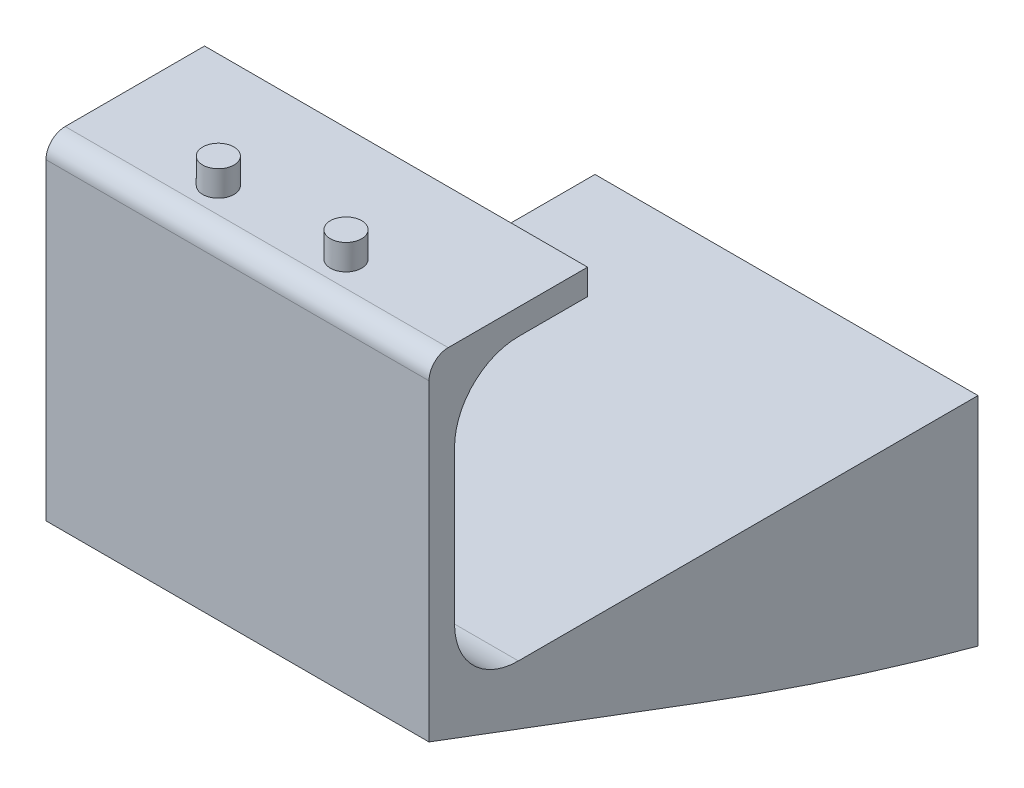
SolidWorks part; units mm, degrees
ref_plane "Front Plane" through (0, 0, 0) normal (0, 0, 1) x (1, 0, 0)
ref_plane "Top Plane" through (0, 0, 0) normal (0, 1, 0) x (1, 0, 0)
ref_plane "Right Plane" through (0, 0, 0) normal (1, 0, 0) x (0, 0, -1)
ref_plane "Plane1" through (18, 0, 0) normal (-1, 0, 0) x (0, -1, 0)
sketch "Sketch1" plane through (18, 0, 0) normal (-1, 0, 0) x (0, -1, 0)
  line L0 (-0.8382, 3) -> (-0.8382, 0)
  line L1 (-0.8382, 0) -> (0, 0)
  arc A0 (0, 0) -> (-0.8382, 3) centre (-236.8592, -64.5597) ccw
extrude "Boss-Extrude1" add sketch "Sketch1" against normal blind 24
sketch "Sketch2" plane through (0, 0.8382, 0) normal (0, 1, 0) x (-1, 0, 0)
  line L0 (-42, 21.6411) -> (-18, 21.6411)
  line L1 (-18, 21.6411) -> (-18, 0)
  line L2 (-18, 0) -> (-42, 0)
  line L3 (-42, 0) -> (-42, 21.6411)
extrude "Boss-Extrude2" add sketch "Sketch2" along normal blind 14.1618
sketch "Sketch3" plane through (42, 0, 0) normal (1, 0, 0) x (0, 0, -1)
  line L0 (0, 15) -> (0, 0)
  line L1 (-21.6411, 6.9904) -> (-43, 15)
  line L2 (-43, 15) -> (0, 15)
  arc A0 (0, 0) -> (-21.6411, 6.9904) centre (64.5597, 236.8592) cw
extrude "Boss-Extrude3" add sketch "Sketch3" along normal blind 3
sketch "Sketch4" plane through (0, 0, 21.6411) normal (0, 0, 1) x (1, 0, 0)
  line L0 (42, 15) -> (42, 6.9904)
  line L1 (42, 6.9904) -> (42, 0.8382)
  line L2 (42, 0.8382) -> (18, 0.8382)
  line L3 (18, 0.8382) -> (18, 6.9904)
  line L4 (18, 6.9904) -> (18, 15)
  line L5 (18, 15) -> (42, 15)
extrude "Boss-Extrude4" add sketch "Sketch4" along normal blind 21.3589
sketch "Sketch5" plane through (0, 15, 0) normal (0, 1, 0) x (-1, 0, 0)
  line L0 (-18, 0) -> (-45, 0)
  line L1 (-45, 0) -> (-45, 43)
  line L2 (-45, 43) -> (-18, 43)
  line L3 (-18, 43) -> (-18, 0)
extrude "Boss-Extrude5" add sketch "Sketch5" along normal blind 24
sketch "Sketch6" plane through (0, 0.8382, 0) normal (0, -1, 0) x (1, 0, 0)
  line L0 (18, 3) -> (42, 3)
  line L1 (42, 3) -> (42, 21.6411)
  line L2 (42, 21.6411) -> (42, 43)
  line L3 (42, 43) -> (18, 43)
  line L4 (18, 43) -> (18, 3)
extrude "Cut-Extrude1" cut sketch "Sketch6" against normal blind 6.1522
sketch "Sketch7" plane through (0, 6.9904, 0) normal (0, -1, 0) x (1, 0, 0)
  line L0 (18, 3) -> (42, 3)
  line L1 (42, 3) -> (42, 43)
  line L2 (42, 43) -> (18, 43)
  line L3 (18, 43) -> (18, 3)
extrude "Cut-Extrude2" cut sketch "Sketch7" against normal blind 8.0096
sketch "Sketch8" plane through (18, 0, 0) normal (-1, 0, 0) x (0, 0, 1)
  line L0 (0, 39) -> (43, 39)
  line L1 (43, 39) -> (43, 15)
  line L2 (43, 15) -> (21.6411, 6.9904)
  line L3 (0, 0) -> (0, 39)
  arc A0 (21.6411, 6.9904) -> (0, 0) centre (-64.5597, 236.8592) cw
extrude "Boss-Extrude6" add sketch "Sketch8" along normal blind 3
sketch "Sketch9" plane through (15, 0, 0) normal (-1, 0, 0) x (0, 0, 1)
  line L0 (0, 17) -> (41, 17)
  line L1 (41, 17) -> (41, 39)
  line L2 (41, 39) -> (0, 39)
  line L3 (0, 39) -> (0, 17)
extrude "Cut-Extrude3" cut sketch "Sketch9" against normal through all
sketch "Sketch10" plane through (0, 39, 0) normal (0, 1, 0) x (-1, 0, 0)
  line L0 (-15, 30.5799) -> (-45, 30.5799)
  line L1 (-45, 30.5799) -> (-45, 43)
  line L2 (-45, 43) -> (-15, 43)
  line L3 (-15, 43) -> (-15, 30.5799)
  line L4 (-15, 0) -> (-15, 41) construction
extrude "Boss-Extrude7" add sketch "Sketch10" along normal blind 2
ref_plane "Plane2" through (0, 0, 36) normal (0, 0, -1) x (-1, 0, 0)
sketch "Sketch11" plane through (0, 0, 36) normal (0, 0, -1) x (-1, 0, 0)
  line L0 (-26.225, 41) -> (-25, 41)
  line L1 (-25, 41) -> (-25, 43)
  line L2 (-25, 43) -> (-26.225, 43)
  line L3 (-26.225, 43) -> (-26.225, 41)
  line L4 (-25, 41) -> (-25, 43) construction
sketch "Sketch12" plane through (0, 0, 36) normal (0, 0, -1) x (-1, 0, 0)
  line L0 (-36.225, 41) -> (-35, 41)
  line L1 (-35, 41) -> (-35, 43)
  line L2 (-35, 43) -> (-36.225, 43)
  line L3 (-36.225, 43) -> (-36.225, 41)
  line L4 (-35, 41) -> (-35, 43) construction
hole_wizard "Ø5.0 (5) Diameter Hole1" positions "Sketch14" profile "Sketch13" hole size "Ø5.0" standard "ANSI Metric"
sketch "Sketch14" plane through (0, 0, 3) normal (0, 0, 1) x (1, 0, 0)
  point P0 (36, 10)
  point P1 (24, 10)
sketch "Sketch13" plane through (36, 10, 3) normal (1, 0, 0) x (0, -1, 0)
  line L0 (0, 0) -> (0, 3)
  line L1 (0, 3) -> (2.5, 3)
  line L2 (2.5, 3) -> (2.5, 0)
  line L5 (2.5, 0) -> (0, 0)
  line L11 (0, -6.35) -> (0, 107.95) construction
  dimension "Thru Hole Dia." = 5
  dimension "Thru Hole Depth" = 3
fillet "Fillet1" radius 1.5 1 edges at (30, 41, 43) tangent propagation no
fillet "Fillet2" radius 5 2 edges at (30, 17, 41) (30, 39, 41) tangent propagation no
sketch "Sketch15" plane through (0, 41, 0) normal (0, 1, 0) x (1, 0, 0)
  line L0 (15, -30.5799) -> (15, -41.5) construction
  line L4 (15, -41.5) -> (45, -41.5) construction
  circle A0 centre (25, -39.5) radius 1.225
  circle A1 centre (35, -39.5) radius 1.225
  dimension "D1" = 10
  dimension "D2" = 10
  dimension "D3" = 2
  dimension "D4" = 2
extrude "Boss-Extrude8" add sketch "Sketch15" along normal blind 2
fillet "Fillet3" radius 3 rebuild error yes
